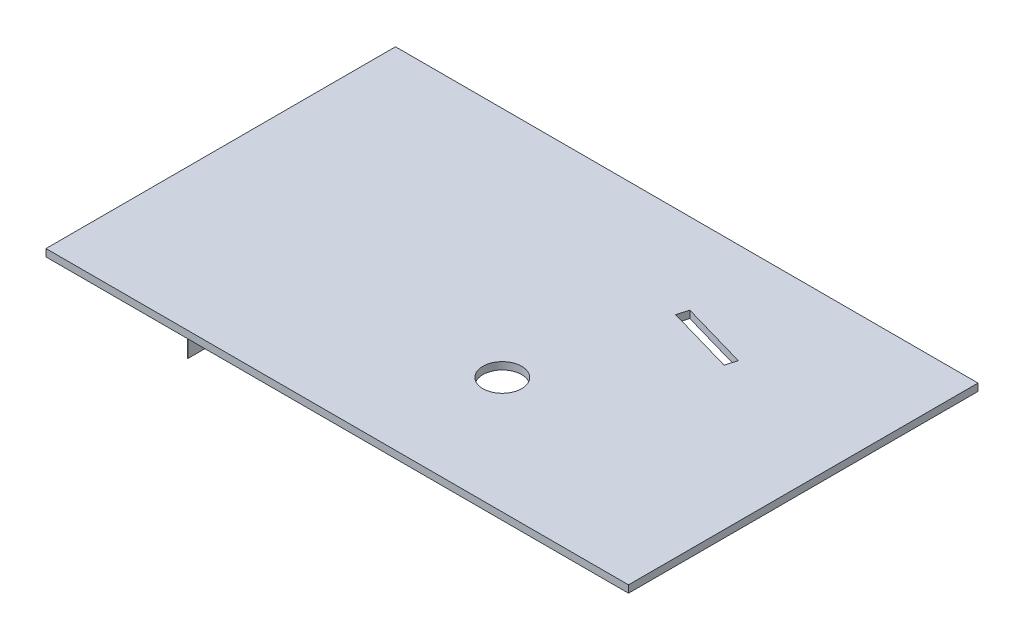
SolidWorks part; units mm, degrees
material "Particle Board"
ref_plane "Front Plane" through (0, 0, 0) normal (0, 0, 1) x (1, 0, 0)
ref_plane "Top Plane" through (0, 0, 0) normal (0, 1, 0) x (1, 0, 0)
ref_plane "Right Plane" through (0, 0, 0) normal (1, 0, 0) x (0, 0, -1)
sketch "Sketch3" plane through (0, 0, 0) normal (0, 1, 0) x (1, 0, 0)
  line L1 (0, 0) -> (-839.8654, 0) construction
  line L2 (0, 0) -> (-451.1992, 260.5) construction
  line L5 (-524, 0) -> (-525.5875, 0)
  line L6 (277.6777, 444.3772) -> (277.6777, 446.248)
  circle A0 centre (0, 0) radius 254 construction
  arc A3 (277.6777, 444.3772) -> (-524, 0) centre (0, 0) ccw
  arc A4 (277.6777, 446.248) -> (-525.5875, 0) centre (0, 0) ccw
  arc A5 (278.5189, 445.7235) -> (-525.5875, 0) centre (0, 0) ccw construction
  dimension "D1" = 524
  dimension "D2" = 1.5875
  dimension "D4" = 122
  dimension "D5" = 508
  dimension "D3" = 30
extrude "Boss-Extrude1" add sketch "Sketch3" along normal blind 50.8
sketch "Sketch4" plane through (0, 50.8, 0) normal (0, 1, 0) x (1, 0, 0)
  line L5 (-889, 609.6) -> (635, 609.6)
  line L6 (-889, 609.6) -> (-889, -304.8)
  line L7 (-889, -304.8) -> (635, -304.8)
  line L8 (635, 609.6) -> (635, -304.8)
  dimension "D1" = 304.8
  dimension "D2" = 1524
  dimension "D3" = 914.4
  dimension "D4" = 635
extrude "Boss-Extrude2" add sketch "Sketch4" along normal blind 19.05
hole_wizard "Ø20.0mm Dowel Hole1" positions "Sketch6" profile "Sketch7" hole size "Ø20.0" standard "ANSI Metric" end condition through all
sketch "Sketch6" plane through (0, 50.8, 0) normal (0, -1, 0) x (-1, 0, 0)
  point P0 (0, 0)
sketch "Sketch7" plane through (0, 50.8, 0) normal (1, 0, 0) x (0, 0, -1)
  line L0 (0, 0) -> (0, 19.05)
  line L1 (0, 19.05) -> (50.8, 19.05)
  line L2 (50.8, 19.05) -> (50.8, 0)
  line L5 (50.8, 0) -> (0, 0)
  line L11 (0, -6.35) -> (0, 107.95) construction
  dimension "Thru Hole Dia." = 101.6
  dimension "Thru Hole Depth" = 19.05
ref_plane "Plane1" through (0, 0, 298.45) normal (0, 0, 1) x (1, 0, 0)
sketch "Sketch8" plane through (0, 0, 0) normal (0, 0, 1) x (1, 0, 0)
  line L0 (-524, 50.8) -> (-524, 0) construction
  line L1 (-525.5875, 50.8) -> (-524, 50.8)
  line L2 (-525.5875, 50.8) -> (-525.5875, 0)
  line L3 (-525.5875, 0) -> (-524, 0)
  line L4 (-524, 50.8) -> (-524, 0)
  line L5 (-525.5875, 50.8) -> (-525.5875, 0) construction
  line L6 (-525.5875, 0) -> (-524, 0) construction
  line L7 (-525.5875, 50.8) -> (-524, 50.8) construction
extrude "Boss-Extrude3" add sketch "Sketch8" along normal up to surface (298.45 mm away) up to plane "Plane1"
sketch "Sketch9" plane through (0, 50.8, 0) normal (0, -1, 0) x (-1, 0, 0)
  line L0 (-92.8177, 397.8388) -> (-270.6511, 346.8459)
  line L1 (-270.6511, 346.8459) -> (-262.382, 318.008)
  line L2 (-262.382, 318.008) -> (-84.5486, 369.0009)
  line L3 (-84.5486, 369.0009) -> (-92.8177, 397.8388)
  line L6 (0, 0) -> (-635, 0) construction
  line L7 (-635, -304.8) -> (-635, 609.6) construction
  dimension "D1" = 185
  dimension "D2" = 30
  dimension "D3" = 16
  dimension "D4" = 262.382
  dimension "D5" = 318.008
extrude "Cut-Extrude1" cut sketch "Sketch9" against normal through all
sketch "Sketch10" plane through (0, 69.85, 0) normal (0, -1, 0) x (-1, 0, 0)
  line L0 (0, 0) -> (-545.6, 0) construction
  line L1 (0, 0) -> (277.6777, 444.3772) construction
  line L2 (0, 0) -> (195.5256, 509.3615) construction
  line L3 (0, 0) -> (94.7424, 537.3111) construction
  circle A0 centre (0, 0) radius 545.6 construction
  dimension "D1" = 11
  dimension "D2" = 11
ref_axis "WHEEL CENTER" through (-965.2, 50.8, 0) along (1, 0, 0)
ref_plane "BASE CENTER" through (-127, 0, 0) normal (1, 0, 0) x (0, 0, -1)
